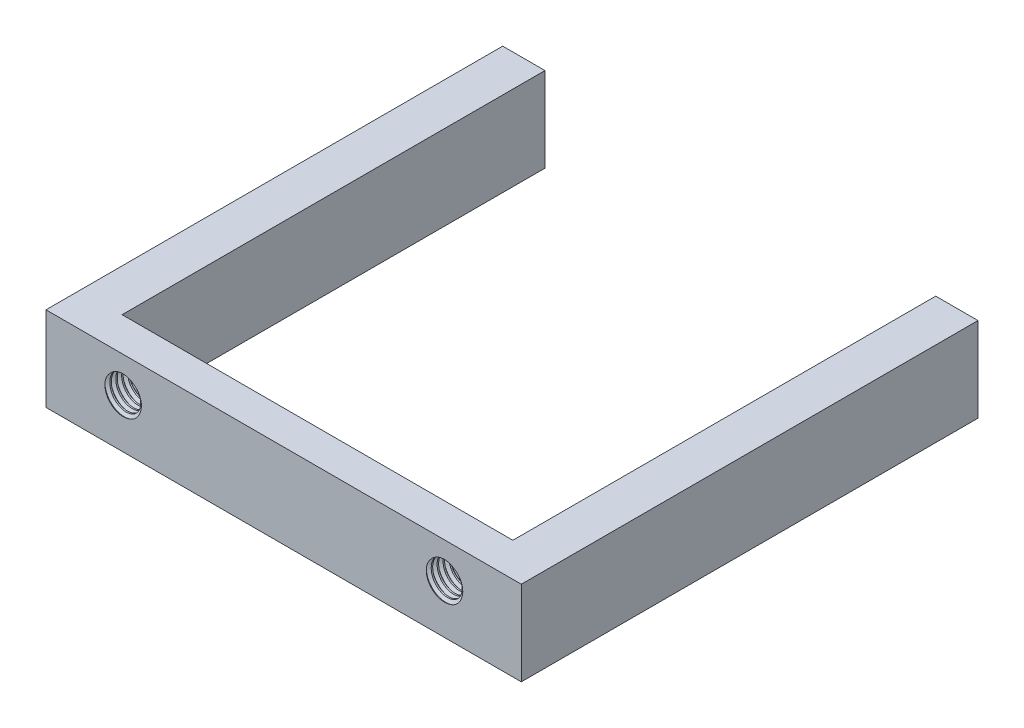
SolidWorks part; units mm, degrees
ref_plane "Front" through (0, 0, 0) normal (0, 0, 1) x (1, 0, 0)
ref_plane "Top" through (0, 0, 0) normal (0, 1, 0) x (1, 0, 0)
ref_plane "Right" through (0, 0, 0) normal (1, 0, 0) x (0, 0, -1)
sketch "Sketch1" plane through (0, 0, 0) normal (0, 0, 1) x (1, 0, 0)
  line L1 (0, 0) -> (56.2, 0)
  line L2 (0, 0) -> (0, 10)
  line L3 (0, 10) -> (56.2, 10)
  line L4 (56.2, 0) -> (56.2, 10)
  circle A0 centre (9.1, 6) radius 2
  circle A1 centre (47.1, 6) radius 2
  dimension "D3" = 4
  dimension "D1" = 56.2
  dimension "D2" = 10
  dimension "D4" = 38
  dimension "D5" = 9.1
  dimension "D6" = 4
  dimension "D7" = 4
extrude "Boss-Extrude1" add sketch "Sketch1" along normal blind 4
sketch "Sketch2" plane through (0, 0, 0) normal (0, -1, 0) x (1, 0, 0)
  line L1 (0, 0) -> (16.6, 0)
  line L2 (0, 0) -> (0, -2)
  line L3 (0, -2) -> (16.6, -2)
  line L4 (16.6, 0) -> (16.6, -2)
  line L5 (56.2, 0) -> (39.6, 0)
  line L6 (56.2, 0) -> (56.2, -2)
  line L7 (56.2, -2) -> (39.6, -2)
  line L8 (39.6, 0) -> (39.6, -2)
  dimension "D1" = 2
  dimension "D2" = 2
  dimension "D3" = 23
extrude "Boss-Extrude2" add sketch "Sketch2" against normal blind 2.9
thread "Thread1" pitch 0.7 method cut profile "Thread Profile1" start angle 0, offset 1, length 5, pitch 0.7, diameter 4
ref_plane "Plane1" through (49.1, 6, -1) normal (0, -1, 0) x (1, 0, 0)
sketch "Thread Profile1" plane through (49.1, 6, -1) normal (0, -1, 0) x (1, 0, 0)
  line L0 (0, 0) -> (0, 0.7) construction
  line L1 (0, 0) -> (0.3789, 0.2187)
  line L2 (0.3789, 0.2187) -> (0.3789, 0.3062)
  line L3 (0.3789, 0.3062) -> (0, 0.525)
  line L4 (0.3789, 0.2625) -> (0, 0.2625) construction
  line L11 (0, 0) -> (0, 0.525)
  point P2 (0, 0)
  dimension "Pitch" = 0.7
  dimension "Profile_Angle" = 60
  dimension "Profile_Land" = 0.0875
  dimension "Profile_Height" = 0.3789
thread "Thread2" pitch 0.7 method cut profile "Thread Profile2" start angle 0, offset 1, length 5, pitch 0.7, diameter 4
ref_plane "Plane2" through (11.1, 6, -1) normal (0, -1, 0) x (1, 0, 0)
sketch "Thread Profile2" plane through (11.1, 6, -1) normal (0, -1, 0) x (1, 0, 0)
  line L0 (0, 0) -> (0, 0.7) construction
  line L1 (0, 0) -> (0.3789, 0.2187)
  line L2 (0.3789, 0.2187) -> (0.3789, 0.3062)
  line L3 (0.3789, 0.3062) -> (0, 0.525)
  line L4 (0.3789, 0.2625) -> (0, 0.2625) construction
  line L11 (0, 0) -> (0, 0.525)
  point P2 (0, 0)
  dimension "Pitch" = 0.7
  dimension "Profile_Angle" = 60
  dimension "Profile_Land" = 0.0875
  dimension "Profile_Height" = 0.3789
sketch "Sketch3" plane through (0, 0, 0) normal (0, 0, -1) x (-1, 0, 0)
  line L0 (-39.6, 0) -> (-56.2, 0) construction
  line L1 (-56.2, 10) -> (-51.2, 10)
  line L2 (-56.2, 10) -> (-56.2, 0)
  line L3 (-56.2, 0) -> (-51.2, 0)
  line L4 (-51.2, 10) -> (-51.2, 0)
  line L5 (0, 0) -> (-16.6, 0) construction
  line L6 (0, 10) -> (-5, 10)
  line L7 (0, 10) -> (0, 0)
  line L8 (0, 0) -> (-5, 0)
  line L9 (-5, 10) -> (-5, 0)
  dimension "D1" = 5
  dimension "D2" = 5
extrude "Boss-Extrude3" add sketch "Sketch3" along normal blind 50
